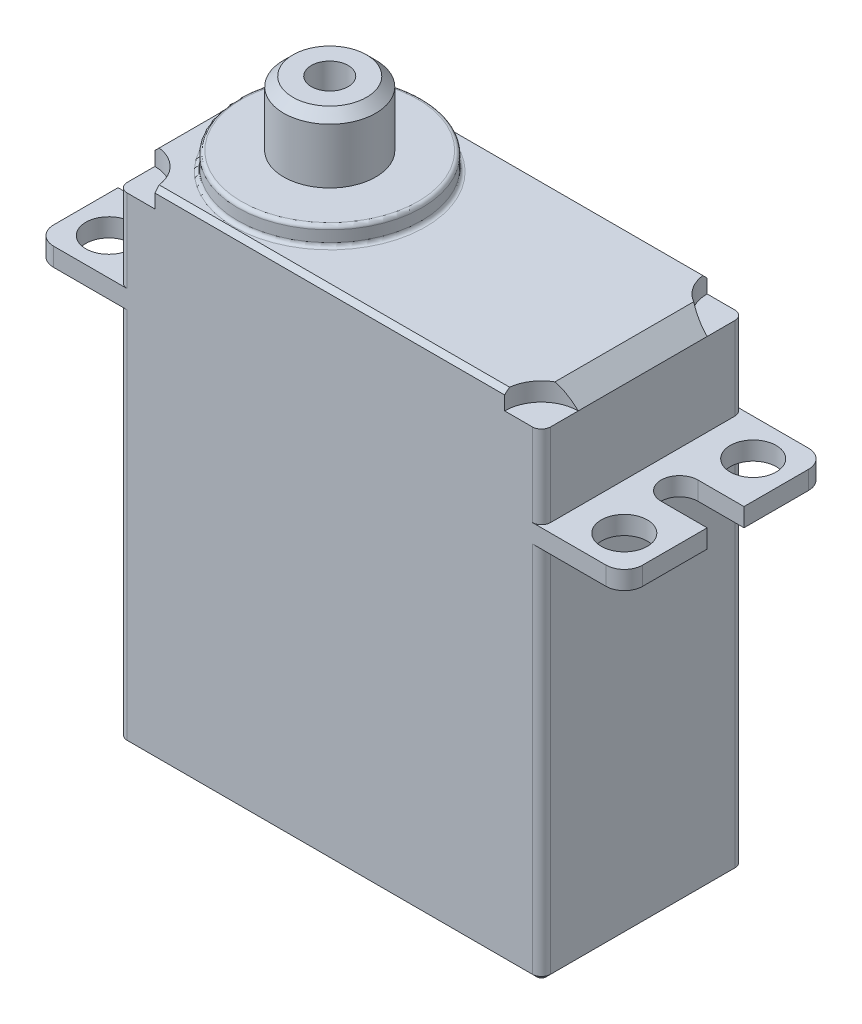
SolidWorks part; units mm, degrees
material "1060-O (SS)"
ref_plane "Front Plane" through (0, 0, 0) normal (0, 0, 1) x (1, 0, 0)
ref_plane "Top Plane" through (0, 0, 0) normal (0, 1, 0) x (1, 0, 0)
ref_plane "Right Plane" through (0, 0, 0) normal (1, 0, 0) x (0, 0, -1)
sketch "Sketch1" plane through (0, 0, 0) normal (0, 1, 0) x (1, 0, 0)
  line L1 (-11.0424, 5.8263) -> (11.9576, 5.8263)
  line L2 (-11.0424, 5.8263) -> (-11.0424, -5.1737)
  line L3 (-11.0424, -5.1737) -> (11.9576, -5.1737)
  line L4 (11.9576, 5.8263) -> (11.9576, -5.1737)
  dimension "D1" = 23
  dimension "D2" = 11
extrude "Boss-Extrude1" add sketch "Sketch1" along normal blind 27
sketch "Sketch2" plane through (0, 27, 0) normal (0, 1, 0) x (1, 0, 0)
  line L0 (-11.0424, 0.3263) -> (11.9576, 0.3263) construction
  line L1 (-11.0424, 5.8263) -> (-11.0424, -5.1737) construction
  line L2 (11.9576, -5.1737) -> (11.9576, 5.8263) construction
  circle A0 centre (-5.0424, 0.3263) radius 5
  point P6 (-5.0424, 0.3263)
  dimension "D2" = 10
  dimension "D1" = 6
extrude "Boss-Extrude2" add sketch "Sketch2" along normal blind 1
fillet "Fillet1" radius 0.2 2 edges at (-5.0424, 27, 4.6737) (-5.0424, 28, 4.6737)
sketch "Sketch3" plane through (0, 28, 0) normal (0, 1, 0) x (1, 0, 0)
  circle A0 centre (-5.0424, 0.3263) radius 2.5
  point P0 (-5.0424, 0.3263)
extrude "Boss-Extrude3" add sketch "Sketch3" along normal blind 3.5
chamfer "Chamfer1" distance 0.5 angle 45 1 edges at (-5.0424, 31.5, 2.1737)
sketch "Sketch4" plane through (0, 31.5, 0) normal (0, 1, 0) x (1, 0, 0)
  circle A0 centre (-5.0424, 0.3263) radius 1
extrude "Cut-Extrude1" cut sketch "Sketch4" against normal blind 3.5
ref_plane "Plane1" through (0, 21.5, 0) normal (0, 1, 0) x (1, 0, 0)
sketch "Sketch5" plane through (0, 21.5, 0) normal (0, 1, 0) x (1, 0, 0)
  line L0 (-11.0424, 5.8263) -> (-11.0424, -5.1737) construction
  line L1 (0.4576, 5.8263) -> (0.4576, -5.1737) construction
  line L2 (-15.5424, 4.8263) -> (-15.5424, 1.3263)
  line L3 (11.9576, 5.8263) -> (-11.0424, 5.8263) construction
  line L4 (-11.0424, -5.1737) -> (11.9576, -5.1737) construction
  line L5 (-14.5424, 5.8263) -> (15.4576, 5.8263)
  line L6 (-14.5424, -5.1737) -> (15.4576, -5.1737)
  line L7 (-15.0424, 0.3263) -> (-11.0424, 0.3263) construction
  line L8 (-15.5424, 1.3263) -> (-13.0424, 1.3263)
  line L9 (15.9576, 0.3263) -> (11.9576, 0.3263) construction
  line L10 (-15.5424, -0.6737) -> (-13.0424, -0.6737)
  line L11 (-15.5424, -0.6737) -> (-15.5424, -4.1737)
  line L12 (16.4576, -0.6737) -> (16.4576, -4.1737)
  line L13 (16.4576, -0.6737) -> (13.9576, -0.6737)
  line L14 (16.4576, 1.3263) -> (13.9576, 1.3263)
  line L15 (16.4576, 4.8263) -> (16.4576, 1.3263)
  arc A0 (-15.5424, -4.1737) -> (-14.5424, -5.1737) centre (-14.5424, -4.1737) ccw
  arc A1 (-15.5424, 4.8263) -> (-14.5424, 5.8263) centre (-14.5424, 4.8263) cw
  arc A2 (-13.0424, -0.6737) -> (-13.0424, 1.3263) centre (-13.0424, 0.3263) ccw
  circle A3 centre (-13.5424, 3.8263) radius 1.25
  circle A4 centre (-13.5424, -3.1737) radius 1.25
  circle A5 centre (14.4576, -3.1737) radius 1.25
  circle A6 centre (14.4576, 3.8263) radius 1.25
  arc A7 (13.9576, -0.6737) -> (13.9576, 1.3263) centre (13.9576, 0.3263) cw
  arc A8 (16.4576, 4.8263) -> (15.4576, 5.8263) centre (15.4576, 4.8263) ccw
  arc A9 (16.4576, -4.1737) -> (15.4576, -5.1737) centre (15.4576, -4.1737) cw
  point P20 (-12.0424, 0.3263)
  point P43 (12.9576, 0.3263)
  dimension "D2" = 1
  dimension "D3" = 2
  dimension "D6" = 2.5
  dimension "D1" = 4.5
  dimension "D4" = 1
  dimension "D5" = 2
extrude "Boss-Extrude4" add sketch "Sketch5" against normal blind 1
fillet "Fillet2" radius 0.5 4 edges at (11.9576, 24.25, -5.8263) (11.9576, 24.25, 5.1737) (-11.0424, 24.25, -5.8263) (-11.0424, 24.25, 5.1737)
sketch "Sketch6" plane through (0, 27, 0) normal (0, 1, 0) x (1, 0, 0)
  line L0 (0.4576, 5.8263) -> (0.4576, -5.1737) construction
  line L1 (11.4576, 5.8263) -> (-10.5424, 5.8263) construction
  line L2 (-10.5424, -5.1737) -> (11.4576, -5.1737) construction
  line L3 (11.9576, 0.3263) -> (-11.0424, 0.3263) construction
  line L4 (11.9576, -4.6737) -> (11.9576, 5.3263) construction
  line L5 (-11.0424, 5.3263) -> (-11.0424, -4.6737) construction
  line L6 (-10.317, 5.8263) -> (-11.0424, 5.8263) construction
  line L7 (-11.0424, 4.91) -> (-11.0424, 5.8263) construction
  circle A0 centre (-11.0424, 5.8263) radius 2
  circle A1 centre (11.9576, 5.8263) radius 2
  circle A2 centre (11.9576, -5.1737) radius 2
  circle A3 centre (-11.0424, -5.1737) radius 2
extrude "Cut-Extrude2" cut sketch "Sketch6" against normal blind 1
chamfer "Chamfer2" distance 1 angle 45 1 edges at (11.9576, 27, -0.3263)
fillet "Fillet3" radius 0.5 4 edges at (-11.0424, 10.25, 5.1737) (11.9576, 10.25, -5.8263) (11.9576, 10.25, 5.1737) (-11.0424, 10.25, -5.8263)
chamfer "Chamfer3" distance 0.25 angle 45 11 edges at (0.4576, 0, -5.8263) (-11.0424, 0, -0.3263) (11.9576, 0, -0.3263) (0.4576, 0, 5.1737) (0.4576, 27, -5.8263) (0.4576, 27, 5.1737) (-11.0424, 27, -0.3263) (-10.896, 0, -5.6798) (11.8111, 0, -5.6798) (-10.896, 0, 5.0273) (11.8111, 0, 5.0273)
